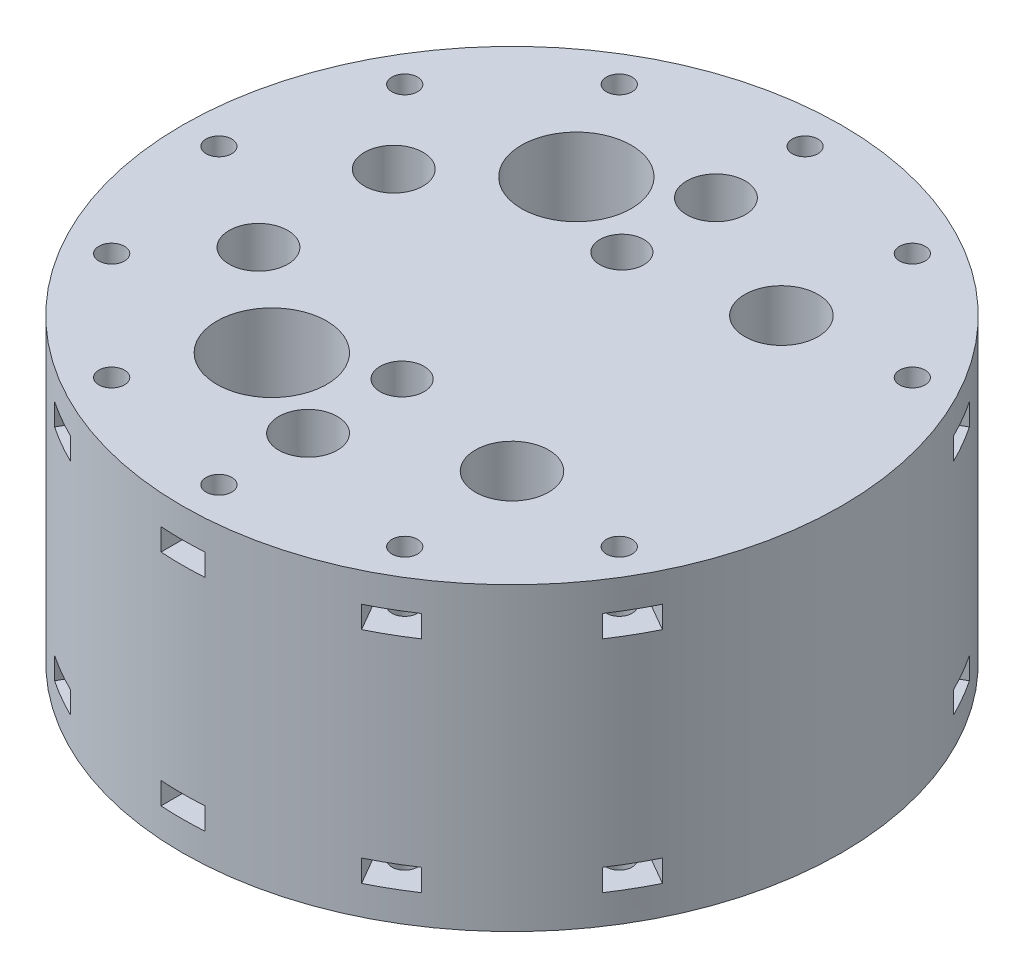
SolidWorks part; units mm, degrees
ref_plane "Front Plane" through (0, 0, 0) normal (0, 0, 1) x (1, 0, 0)
ref_plane "Top Plane" through (0, 0, 0) normal (0, 1, 0) x (1, 0, 0)
ref_plane "Right Plane" through (0, 0, 0) normal (1, 0, 0) x (0, 0, -1)
sketch "Sketch1" plane through (0, 0, 0) normal (0, 1, 0) x (1, 0, 0)
  line L0 (-43.0464, 0) -> (41.9462, 0) construction
  line L1 (0, 43.1152) -> (0, -41.8775) construction
  circle A1 centre (0, 0) radius 45
  dimension "D2" = 90
extrude "Boss-Extrude1" add sketch "Sketch1" along normal blind 41
sketch "Sketch2" plane through (0, 0, 0) normal (0, -1, 0) x (1, 0, 0)
  circle A0 centre (0, 0) radius 35
  dimension "D1" = 70
extrude "Cut-Extrude1" cut sketch "Sketch2" against normal blind 27
sketch "Sketch3" plane through (0, 27, 0) normal (0, -1, 0) x (1, 0, 0)
  line L0 (35, 0) -> (-35, 0) construction
  line L1 (0, -35) -> (0, 35) construction
  line L3 (37.5324, -10) -> (-17.4676, -10)
  line L4 (37.5324, -10) -> (37.5324, 10)
  line L5 (37.5324, 10) -> (-17.4676, 10)
  line L6 (-17.4676, -10) -> (-17.4676, 10)
  circle A0 centre (0, 0) radius 35 construction
  circle A1 centre (0, 0) radius 35 construction
  dimension "D1" = 20
  dimension "D2" = 55
  dimension "D3" = 10
  dimension "D4" = 37.5324
extrude "Cut-Extrude2" cut sketch "Sketch3" against normal blind 2.5 and the other way up to next
sketch "Sketch4" plane through (0, 29.5, 0) normal (0, -1, 0) x (1, 0, 0)
  line L0 (37.5324, 0) -> (-17.4676, 0) construction
  line L1 (37.5324, 10) -> (37.5324, -10) construction
  line L2 (-17.4676, 10) -> (-17.4676, -10) construction
  line L3 (0, -10) -> (0, 10) construction
  line L4 (-17.4676, -10) -> (33.541, -10) construction
  line L5 (33.541, 10) -> (-17.4676, 10) construction
  line L7 (30.3722, -10) -> (-10.4278, -10)
  line L8 (30.3722, -10) -> (30.3722, 10)
  line L9 (30.3722, 10) -> (-10.4278, 10)
  line L10 (-10.4278, -10) -> (-10.4278, 10)
  dimension "D1" = 20
  dimension "D2" = 40.8
  dimension "D3" = 30.3722
  dimension "D4" = 10
extrude "Cut-Extrude3" cut sketch "Sketch4" against normal blind 10.5
sketch "Sketch8" plane through (0, 27, 0) normal (0, -1, 0) x (1, 0, 0)
  line L0 (-17.4676, 0) -> (-35, 0) construction
  line L1 (-17.4676, 10) -> (-17.4676, -10) construction
  line L2 (8.0367, 10) -> (8.0367, 34.0648) construction
  line L3 (33.541, 10) -> (-17.4676, 10) construction
  line L4 (8.0367, -10) -> (8.0367, -29.3194) construction
  line L5 (-17.4676, -10) -> (33.541, -10) construction
  line L6 (6.5367, 10) -> (6.5367, 34.3842)
  line L7 (9.5367, 10) -> (9.5367, 33.6757)
  line L8 (9.5367, 10) -> (6.5367, 10)
  line L9 (9.5367, -10) -> (6.5367, -10)
  line L10 (6.5367, -10) -> (6.5367, -34.3842)
  line L11 (9.5367, -10) -> (9.5367, -33.6757)
  line L12 (-17.4676, 1.5) -> (-34.9678, 1.5)
  line L13 (-17.4676, -1.5) -> (-34.9678, -1.5)
  line L14 (-17.4676, 1.5) -> (-17.4676, -1.5)
  arc A0 (33.541, 10) -> (33.541, -10) centre (0, 0) ccw construction
  arc A1 (9.5367, 33.6757) -> (6.5367, 34.3842) centre (7.9531, 33.6757) ccw
  arc A2 (9.5367, -33.6757) -> (6.5367, -34.3842) centre (7.9531, -33.6757) cw
  arc A3 (-34.9678, 1.5) -> (-34.9678, -1.5) centre (-34.9678, 0) ccw
  dimension "D3" = 1.5
  dimension "D1" = 1.5
  dimension "D2" = 1.5
  dimension "D4" = 1.5
extrude "Boss-Extrude2" add sketch "Sketch8" along normal through all
sketch "Sketch13" plane through (0, 27, 0) normal (0, -1, 0) x (1, 0, 0)
  line L0 (0, 0) -> (0, 35) construction
  line L1 (0, 0) -> (-17.5, 30.3109) construction
  line L2 (0, 0) -> (-41.2446, 0) construction
  line L3 (-32.8892, 11.9707) -> (0, 0) construction
  line L5 (0, 0) -> (24.7487, 24.7487) construction
  arc A0 (6.5367, 34.3842) -> (-34.9678, 1.5) centre (0, 0) ccw construction
  circle A1 centre (-12, 20.7846) radius 7.5
  circle A2 centre (-25.3717, 9.2345) radius 4
  arc A3 (33.541, 10) -> (9.5367, 33.6757) centre (0, 0) ccw construction
  circle A4 centre (18.3848, 18.3848) radius 5
  circle A5 centre (18.3848, -18.3848) radius 5
  circle A6 centre (-12, -20.7846) radius 7.5
  circle A7 centre (-25.3717, -9.2345) radius 4
  circle A8 centre (0, -15) radius 3
  circle A9 centre (0, -27.8351) radius 4
  circle A10 centre (0, 27.8351) radius 4
  circle A11 centre (0, 15) radius 3
  dimension "D3" = 15
  dimension "D6" = 8
  dimension "D8" = 10
  dimension "D10" = 8
  dimension "D11" = 6
  dimension "D1" = 30
  dimension "D2" = 20
  dimension "D4" = 27
  dimension "D5" = 24
  dimension "D7" = 45
  dimension "D9" = 26
  dimension "D12" = 15
extrude "Cut-Extrude7" cut sketch "Sketch13" against normal through all
sketch "Sketch15" plane through (0, 0, -1.5) normal (0, 0, -1) x (-1, 0, 0)
  line L0 (34.9678, 0) -> (17.4676, 27)
  line L1 (17.4676, 27) -> (17.4676, 0)
  line L3 (17.4676, 0) -> (34.9678, 0)
extrude "Cut-Extrude8" cut sketch "Sketch15" against normal blind 3
sketch "Sketch16" plane through (0, 29.5, 0) normal (0, -1, 0) x (1, 0, 0)
  line L0 (-17.4676, 0) -> (37.5324, 0) construction
  line L1 (-17.4676, 10) -> (-17.4676, -10) construction
  line L2 (37.5324, -10) -> (37.5324, 10) construction
  line L3 (30.3722, -0.8) -> (37.5324, -0.8)
  line L4 (-10.4278, -0.8) -> (-17.4676, -0.8)
  line L5 (-10.4278, 10) -> (-10.4278, -10) construction
  line L6 (-10.4278, 0.8) -> (-17.4676, 0.8)
  line L7 (-17.4676, 0.8) -> (-17.4676, -0.8)
  line L8 (-10.4278, 0.8) -> (-10.4278, -0.8)
  line L9 (30.3722, -10) -> (30.3722, 10) construction
  line L10 (30.3722, 0.8) -> (37.5324, 0.8)
  line L11 (37.5324, 0.8) -> (37.5324, -0.8)
  line L12 (30.3722, 0.8) -> (30.3722, -0.8)
  dimension "D1" = 0.8
extrude "Cut-Extrude10" cut sketch "Sketch16" against normal blind 3
sketch "Sketch27" plane through (0, 0, 0) normal (0, -1, 0) x (1, 0, 0)
  line L0 (0, 0) -> (0, -53.17) construction
  line L1 (0, 0) -> (47.7582, -27.5732) construction
  line L3 (31.641, -18.2679) -> (31.641, -21.7321) construction
  line L4 (31.641, -21.7321) -> (34.641, -23.4641) construction
  line L5 (34.641, -23.4641) -> (37.641, -21.7321) construction
  line L6 (37.641, -21.7321) -> (37.641, -18.2679) construction
  line L7 (37.641, -18.2679) -> (34.641, -16.5359) construction
  line L8 (34.641, -16.5359) -> (31.641, -18.2679) construction
  circle A0 centre (0, 0) radius 40 construction
  circle A1 centre (34.641, -20) radius 1.75
  circle A2 centre (0, 0) radius 35 construction
  circle A3 centre (34.641, -20) radius 3 construction
  circle A4 centre (20, -34.641) radius 1.75
  circle A5 centre (0, -40) radius 1.75
  circle A6 centre (-20, -34.641) radius 1.75
  circle A7 centre (-34.641, -20) radius 1.75
  circle A8 centre (-40, 0) radius 1.75
  circle A9 centre (-34.641, 20) radius 1.75
  circle A10 centre (-20, 34.641) radius 1.75
  circle A11 centre (0, 40) radius 1.75
  circle A12 centre (20, 34.641) radius 1.75
  circle A13 centre (34.641, 20) radius 1.75
  circle A15 centre (40, 0) radius 1.75 [skipped]
  point P28 (0, 0)
  point P41 (0, 0)
  dimension "D1" = 80
  dimension "D3" = 3.5
  dimension "D4" = 70
  dimension "D5" = 6
  dimension "D6" = 12
  dimension "D2" = 60
extrude "Cut-Extrude15" cut sketch "Sketch27" against normal through all
ref_plane "Plane1" through (0, 37, 0) normal (0, 1, 0) x (1, 0, 0)
sketch "Sketch28" plane through (0, 37, 0) normal (0, 1, 0) x (1, 0, 0)
  line L0 (0, 0) -> (-54.493, 0) construction
  line L1 (-31.641, 18.2679) -> (-31.641, 21.7321)
  line L2 (-36.5359, 0) -> (-38.2679, 3)
  line L3 (-38.2679, 3) -> (-44.8999, 3)
  line L4 (-31.641, 21.7321) -> (-37.3844, 25.048)
  line L5 (-40.3844, 19.8519) -> (-34.641, 16.5359)
  line L6 (-44.8999, -3) -> (-38.2679, -3)
  line L7 (-38.2679, -3) -> (-36.5359, 0)
  line L8 (-43.4641, 0) -> (-42.5981, -1.5) [skipped]
  line L9 (-41.7321, 3) -> (-42.5981, 1.5) [skipped]
  line L10 (-34.641, 16.5359) -> (-31.641, 18.2679)
  line L11 (-18.2679, 31.641) -> (-16.5359, 34.641)
  line L12 (-16.5359, 34.641) -> (-19.8519, 40.3844)
  line L13 (-25.048, 37.3844) -> (-21.7321, 31.641)
  line L14 (-21.7321, 31.641) -> (-18.2679, 31.641)
  line L15 (0, 36.5359) -> (3, 38.2679)
  line L16 (3, 38.2679) -> (3, 44.8999)
  line L17 (-3, 44.8999) -> (-3, 38.2679)
  line L18 (-3, 38.2679) -> (0, 36.5359)
  line L19 (18.2679, 31.641) -> (21.7321, 31.641)
  line L20 (21.7321, 31.641) -> (25.048, 37.3844)
  line L21 (19.8519, 40.3844) -> (16.5359, 34.641)
  line L22 (16.5359, 34.641) -> (18.2679, 31.641)
  line L23 (31.641, 18.2679) -> (34.641, 16.5359)
  line L24 (34.641, 16.5359) -> (40.3844, 19.8519)
  line L25 (37.3844, 25.048) -> (31.641, 21.7321)
  line L26 (31.641, 21.7321) -> (31.641, 18.2679)
  line L31 (31.641, -18.2679) -> (31.641, -21.7321)
  line L32 (31.641, -21.7321) -> (37.3844, -25.048)
  line L33 (40.3844, -19.8519) -> (34.641, -16.5359)
  line L34 (34.641, -16.5359) -> (31.641, -18.2679)
  line L35 (18.2679, -31.641) -> (16.5359, -34.641)
  line L36 (16.5359, -34.641) -> (19.8519, -40.3844)
  line L37 (25.048, -37.3844) -> (21.7321, -31.641)
  line L38 (21.7321, -31.641) -> (18.2679, -31.641)
  line L39 (0, -36.5359) -> (-3, -38.2679)
  line L40 (-3, -38.2679) -> (-3, -44.8999)
  line L41 (3, -44.8999) -> (3, -38.2679)
  line L42 (3, -38.2679) -> (0, -36.5359)
  line L43 (-18.2679, -31.641) -> (-21.7321, -31.641)
  line L44 (-21.7321, -31.641) -> (-25.048, -37.3844)
  line L45 (-19.8519, -40.3844) -> (-16.5359, -34.641)
  line L46 (-16.5359, -34.641) -> (-18.2679, -31.641)
  line L47 (-31.641, -18.2679) -> (-34.641, -16.5359)
  line L48 (-34.641, -16.5359) -> (-40.3844, -19.8519)
  line L49 (-37.3844, -25.048) -> (-31.641, -21.7321)
  line L50 (-31.641, -21.7321) -> (-31.641, -18.2679)
  line L51 (36.5359, 0) -> (38.2679, -3) [skipped]
  line L52 (38.2679, -3) -> (44.8999, -3) [skipped]
  line L53 (44.8999, 3) -> (38.2679, 3) [skipped]
  line L54 (38.2679, 3) -> (36.5359, 0) [skipped]
  arc A0 (-44.8999, 3) -> (-44.8999, -3) centre (0, 0) ccw
  circle A1 centre (-40, 0) radius 3 construction
  arc A2 (-37.3844, 25.048) -> (-40.3844, 19.8519) centre (0, 0) ccw
  circle A3 centre (-34.641, 20) radius 3 construction
  arc A4 (-19.8519, 40.3844) -> (-25.048, 37.3844) centre (0, 0) ccw
  circle A5 centre (-20, 34.641) radius 3 construction
  arc A6 (3, 44.8999) -> (-3, 44.8999) centre (0, 0) ccw
  circle A7 centre (0, 40) radius 3 construction
  arc A8 (25.048, 37.3844) -> (19.8519, 40.3844) centre (0, 0) ccw
  circle A9 centre (20, 34.641) radius 3 construction
  arc A10 (40.3844, 19.8519) -> (37.3844, 25.048) centre (0, 0) ccw
  circle A11 centre (34.641, 20) radius 3 construction
  arc A14 (37.3844, -25.048) -> (40.3844, -19.8519) centre (0, 0) ccw
  circle A15 centre (34.641, -20) radius 3 construction
  arc A16 (19.8519, -40.3844) -> (25.048, -37.3844) centre (0, 0) ccw
  circle A17 centre (20, -34.641) radius 3 construction
  arc A18 (-3, -44.8999) -> (3, -44.8999) centre (0, 0) ccw
  circle A19 centre (0, -40) radius 3 construction
  arc A20 (-25.048, -37.3844) -> (-19.8519, -40.3844) centre (0, 0) ccw
  circle A21 centre (-20, -34.641) radius 3 construction
  arc A22 (-40.3844, -19.8519) -> (-37.3844, -25.048) centre (0, 0) ccw
  circle A23 centre (-34.641, -20) radius 3 construction
  arc A24 (44.8999, -3) -> (44.8999, 3) centre (0, 0) ccw [skipped]
  circle A25 centre (40, 0) radius 3 construction
  point P94 (0, 0)
  dimension "D1" = 90
  dimension "D2" = 6
  dimension "D3" = 12
extrude "Cut-Extrude17" cut sketch "Sketch28" against normal blind 3
ref_plane "Plane2" through (0, 4, 0) normal (0, -1, 0) x (-1, 0, 0)
sketch "Sketch30" plane through (0, 4, 0) normal (0, -1, 0) x (-1, 0, 0)
  line L0 (0, 0) -> (56.1913, 0) construction
  line L1 (31.641, -18.2679) -> (31.641, -21.7321)
  line L2 (36.5359, 0) -> (38.2679, -3)
  line L3 (38.2679, -3) -> (44.8999, -3)
  line L4 (31.641, -21.7321) -> (37.3844, -25.048)
  line L5 (40.3844, -19.8519) -> (34.641, -16.5359)
  line L6 (44.8999, 3) -> (38.2679, 3)
  line L7 (38.2679, 3) -> (36.5359, 0)
  line L8 (43.4641, 0) -> (42.5981, 1.5) [skipped]
  line L9 (41.7321, -3) -> (42.5981, -1.5) [skipped]
  line L10 (34.641, -16.5359) -> (31.641, -18.2679)
  line L11 (18.2679, -31.641) -> (16.5359, -34.641)
  line L12 (16.5359, -34.641) -> (19.8519, -40.3844)
  line L13 (25.048, -37.3844) -> (21.7321, -31.641)
  line L14 (21.7321, -31.641) -> (18.2679, -31.641)
  line L15 (0, -36.5359) -> (-3, -38.2679)
  line L16 (-3, -38.2679) -> (-3, -44.8999)
  line L17 (3, -44.8999) -> (3, -38.2679)
  line L18 (3, -38.2679) -> (0, -36.5359)
  line L19 (-18.2679, -31.641) -> (-21.7321, -31.641)
  line L20 (-21.7321, -31.641) -> (-25.048, -37.3844)
  line L21 (-19.8519, -40.3844) -> (-16.5359, -34.641)
  line L22 (-16.5359, -34.641) -> (-18.2679, -31.641)
  line L23 (-31.641, -18.2679) -> (-34.641, -16.5359)
  line L24 (-34.641, -16.5359) -> (-40.3844, -19.8519)
  line L25 (-37.3844, -25.048) -> (-31.641, -21.7321)
  line L26 (-31.641, -21.7321) -> (-31.641, -18.2679)
  line L31 (-31.641, 18.2679) -> (-31.641, 21.7321)
  line L32 (-31.641, 21.7321) -> (-37.3844, 25.048)
  line L33 (-40.3844, 19.8519) -> (-34.641, 16.5359)
  line L34 (-34.641, 16.5359) -> (-31.641, 18.2679)
  line L35 (-18.2679, 31.641) -> (-16.5359, 34.641)
  line L36 (-16.5359, 34.641) -> (-19.8519, 40.3844)
  line L37 (-25.048, 37.3844) -> (-21.7321, 31.641)
  line L38 (-21.7321, 31.641) -> (-18.2679, 31.641)
  line L39 (0, 36.5359) -> (3, 38.2679)
  line L40 (3, 38.2679) -> (3, 44.8999)
  line L41 (-3, 44.8999) -> (-3, 38.2679)
  line L42 (-3, 38.2679) -> (0, 36.5359)
  line L43 (18.2679, 31.641) -> (21.7321, 31.641)
  line L44 (21.7321, 31.641) -> (25.048, 37.3844)
  line L45 (19.8519, 40.3844) -> (16.5359, 34.641)
  line L46 (16.5359, 34.641) -> (18.2679, 31.641)
  line L47 (31.641, 18.2679) -> (34.641, 16.5359)
  line L48 (34.641, 16.5359) -> (40.3844, 19.8519)
  line L49 (37.3844, 25.048) -> (31.641, 21.7321)
  line L50 (31.641, 21.7321) -> (31.641, 18.2679)
  line L51 (-36.5359, 0) -> (-38.2679, 3) [skipped]
  line L52 (-38.2679, 3) -> (-44.8999, 3) [skipped]
  line L53 (-44.8999, -3) -> (-38.2679, -3) [skipped]
  line L54 (-38.2679, -3) -> (-36.5359, 0) [skipped]
  arc A0 (44.8999, -3) -> (44.8999, 3) centre (0, 0) ccw
  circle A1 centre (40, 0) radius 3 construction
  arc A2 (37.3844, -25.048) -> (40.3844, -19.8519) centre (0, 0) ccw
  circle A3 centre (34.641, -20) radius 3 construction
  arc A4 (19.8519, -40.3844) -> (25.048, -37.3844) centre (0, 0) ccw
  circle A5 centre (20, -34.641) radius 3 construction
  arc A6 (-3, -44.8999) -> (3, -44.8999) centre (0, 0) ccw
  circle A7 centre (0, -40) radius 3 construction
  arc A8 (-25.048, -37.3844) -> (-19.8519, -40.3844) centre (0, 0) ccw
  circle A9 centre (-20, -34.641) radius 3 construction
  arc A10 (-40.3844, -19.8519) -> (-37.3844, -25.048) centre (0, 0) ccw
  circle A11 centre (-34.641, -20) radius 3 construction
  arc A14 (-37.3844, 25.048) -> (-40.3844, 19.8519) centre (0, 0) ccw
  circle A15 centre (-34.641, 20) radius 3 construction
  arc A16 (-19.8519, 40.3844) -> (-25.048, 37.3844) centre (0, 0) ccw
  circle A17 centre (-20, 34.641) radius 3 construction
  arc A18 (3, 44.8999) -> (-3, 44.8999) centre (0, 0) ccw
  circle A19 centre (0, 40) radius 3 construction
  arc A20 (25.048, 37.3844) -> (19.8519, 40.3844) centre (0, 0) ccw
  circle A21 centre (20, 34.641) radius 3 construction
  arc A22 (40.3844, 19.8519) -> (37.3844, 25.048) centre (0, 0) ccw
  circle A23 centre (34.641, 20) radius 3 construction
  arc A24 (-44.8999, 3) -> (-44.8999, -3) centre (0, 0) ccw [skipped]
  circle A25 centre (-40, 0) radius 3 construction
  point P94 (0, 0)
  dimension "D1" = 90
  dimension "D2" = 6
  dimension "D3" = 12
extrude "Cut-Extrude19" cut sketch "Sketch30" against normal blind 3
